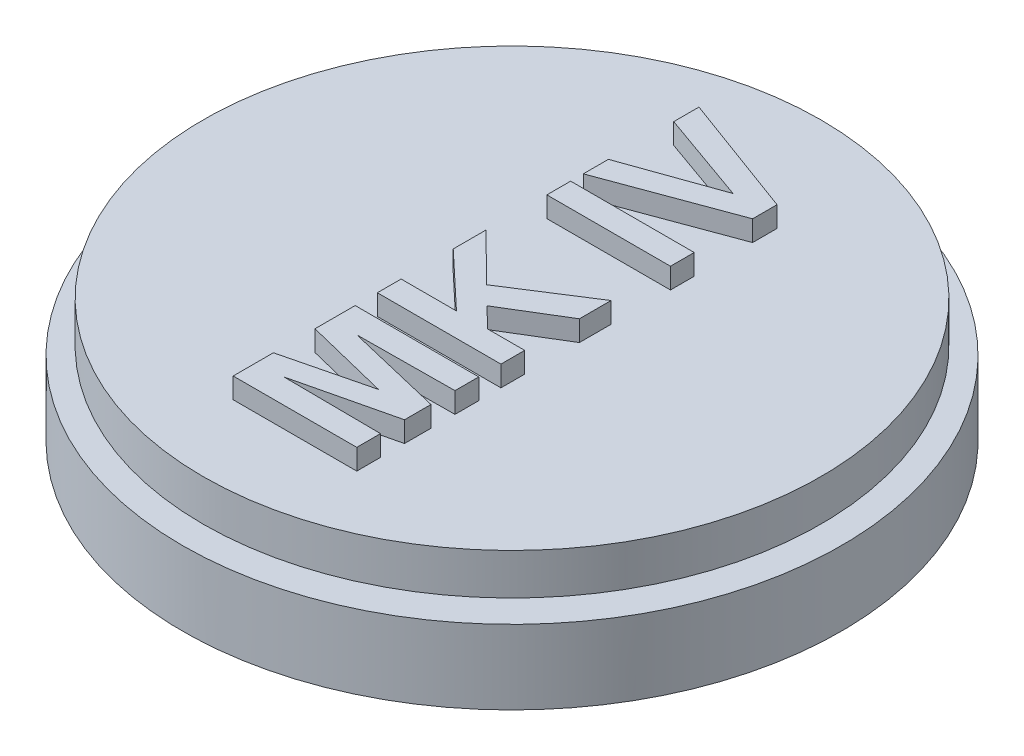
SolidWorks part; units mm, degrees
ref_plane "Спереди" through (0, 0, 0) normal (0, 0, 1) x (1, 0, 0)
ref_plane "Сверху" through (0, 0, 0) normal (0, 1, 0) x (1, 0, 0)
ref_plane "Справа" through (0, 0, 0) normal (1, 0, 0) x (0, 0, -1)
sketch "Sketch1" plane through (0, 0, 0) normal (0, 1, 0) x (1, 0, 0)
  circle A0 centre (0, 0) radius 12.3
  dimension "D1" = 24.6
extrude "Boss-Extrude1" add sketch "Sketch1" along normal blind 4
sketch "Sketch2" plane through (0, 4, 0) normal (0, 1, 0) x (1, 0, 0)
  circle A0 centre (0, 0) radius 15
  dimension "D1" = 30
extrude "Boss-Extrude2" add sketch "Sketch2" along normal blind 2
chamfer "Chamfer1" distance 0.5 angle 70 1 edges at (0, 0, 12.3) first distance on face at (0, 0, 12.3)
sketch "Sketch3" plane through (0, 6, 0) normal (0, 1, 0) x (1, 0, 0)
  line L0 (3.5, -14.586) -> (3.5, 14.586) construction
  line L1 (0, -15) -> (0, 15) construction
  circle A0 centre (0, 0) radius 15 construction
  text T0 "MK IV" font "Arial" height 6
  dimension "D1" = 3.5
extrude "Boss-Extrude3" add sketch "Sketch3" along normal blind 1
sketch "Sketch4" plane through (0, 0, 0) normal (0, -1, 0) x (1, 0, 0)
  circle A0 centre (0, 0) radius 12.8
  circle A1 centre (0, 0) radius 16
  circle A2 centre (0, 0) radius 11.8 construction
  circle A3 centre (0, 0) radius 15 construction
  dimension "D1" = 1
  dimension "D2" = 1
extrude "Boss-Extrude4" add sketch "Sketch4" against normal offset from surface (3.6 mm away) 0.4 separate body up to face at (0, 4, 12.3)
